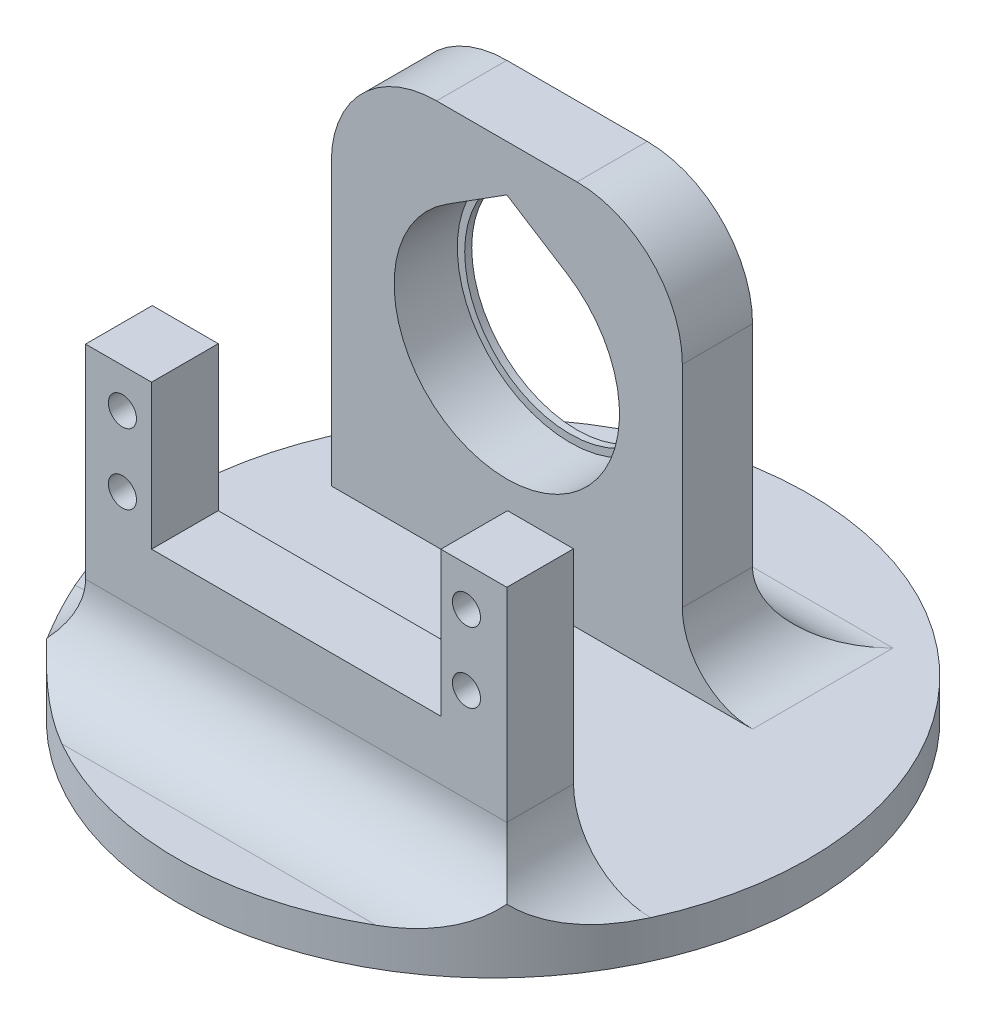
SolidWorks part; units mm, degrees
ref_plane "Front Plane" through (0, 0, 0) normal (0, 0, 1) x (1, 0, 0)
ref_plane "Top Plane" through (0, 0, 0) normal (0, 1, 0) x (1, 0, 0)
ref_plane "Right Plane" through (0, 0, 0) normal (1, 0, 0) x (0, 0, -1)
sketch "Sketch1" plane through (0, 0, 0) normal (0, 1, 0) x (1, 0, 0)
  circle A0 centre (0, 0) radius 45
  dimension "D1" = 90
extrude "Boss-Extrude1" add sketch "Sketch1" along normal blind 5.4
sketch "Sketch2" plane through (0, 0, 0) normal (0, -1, 0) x (1, 0, 0)
  circle A0 centre (0, 0) radius 10.5
  dimension "D1" = 21
extrude "Cut-Extrude1" cut sketch "Sketch2" against normal blind 3.4
sketch "Sketch4" plane through (0, 5.4, 0) normal (0, 1, 0) x (1, 0, 0)
  circle A0 centre (0, 0) radius 4.875
  dimension "D1" = 9.75
extrude "Cut-Extrude2" cut sketch "Sketch4" against normal blind 22.5
sketch "Sketch5" plane through (0, 5.4, 0) normal (0, 1, 0) x (1, 0, 0)
  line L1 (-30, -18.541) -> (30, -18.541)
  line L2 (-30, -18.541) -> (-30, -28.041)
  line L3 (-30, -28.041) -> (30, -28.041)
  line L4 (30, -18.541) -> (30, -28.041)
  point P4 (0, -18.541)
  dimension "D1" = 60
  dimension "D2" = 18.541
  dimension "D3" = 9.5
extrude "Boss-Extrude2" add sketch "Sketch5" along normal blind 40
sketch "Sketch6" plane through (0, 45.4, 0) normal (0, 1, 0) x (1, 0, 0)
  line L1 (-20.6, 8.6801) -> (20.6, 8.6801)
  line L2 (-20.6, 8.6801) -> (-20.6, -51.928)
  line L3 (-20.6, -51.928) -> (20.6, -51.928)
  line L4 (20.6, 8.6801) -> (20.6, -51.928)
  line L5 (-20.6, 8.6801) -> (20.6, -51.928) construction
  line L6 (-20.6, -51.928) -> (20.6, 8.6801) construction
  point P0 (0, -21.624)
  dimension "D1" = 41.2
extrude "Cut-Extrude3" cut sketch "Sketch6" against normal blind 20.6
fillet "Fillet2" radius 11 3 edges at (0, 5.4, 28.041) (-30, 5.4, 23.291) (30, 5.4, 23.291)
sketch "Sketch7" plane through (0, 5.4, 0) normal (0, 1, 0) x (1, 0, 0)
  line L0 (-10, 4.459) -> (0.8781, -33.8396) construction
  line L1 (-35, 21.959) -> (15, 21.959)
  line L2 (-35, 21.959) -> (-35, 11.959)
  line L3 (-35, 11.959) -> (15, 11.959)
  line L4 (15, 21.959) -> (15, 11.959)
  line L5 (-35, 21.959) -> (15, 11.959) construction
  line L6 (-35, 11.959) -> (15, 21.959) construction
  line L7 (-10, 4.459) -> (0.8781, -33.8396) construction
  point P0 (-10, 16.959)
  point P14 (-10, 4.459)
  dimension "D1" = 50
  dimension "D2" = 10
  dimension "D3" = 12.5
extrude "Boss-Extrude3" add sketch "Sketch7" along normal blind 55
sketch "Sketch8" plane through (0, 0, -21.959) normal (0, 0, -1) x (-1, 0, 0)
  line L0 (35, 60.4) -> (35, 5.4) construction
  line L2 (-15, 5.4) -> (35, 5.4) construction
  circle A0 centre (10.0003, 34.8) radius 15
  dimension "D1" = 24.9997
  dimension "D3" = 30
  dimension "D2" = 29.4
extrude "Cut-Extrude4" cut sketch "Sketch8" against normal blind 18.6
sketch "Sketch9" plane through (0, 0, -11.959) normal (0, 0, 1) x (1, 0, 0)
  line L0 (-10.0003, 34.8) -> (-10.0003, 53.8) construction
  line L1 (-10.0003, 53.8) -> (-18.5899, 48.358)
  line L2 (-10.0003, 53.8) -> (-1.4106, 48.358)
  arc A0 (-18.5899, 48.358) -> (-1.4106, 48.358) centre (-10.0003, 34.8) ccw
  point P6 (0, 0)
  point P7 (0, 0)
  dimension "D1" = 32.1
  dimension "D2" = 19
extrude "Cut-Extrude5" cut sketch "Sketch9" against normal offset from surface (9 mm away) 1 up to face at (-25.0003, 34.8, -21.959)
fillet "Fillet4" radius 15 2 edges at (-35, 60.4, -16.959) (15, 60.4, -16.959)
fillet "Fillet5" radius 10 2 edges at (-10, 5.4, -21.959) (15, 5.4, -16.959)
sketch "Sketch10" plane through (0, 5.4, 0) normal (0, 1, 0) x (1, 0, 0)
  circle A0 centre (7, 0) radius 1.65
  circle A1 centre (0, 7) radius 1.65
  circle A2 centre (-7, 0) radius 1.65
  circle A3 centre (0, -7) radius 1.65
  dimension "D1" = 7
  dimension "D2" = 7
  dimension "D5" = 3.3
  dimension "D3" = 7
  dimension "D4" = 7
extrude "Cut-Extrude6" cut sketch "Sketch10" against normal through all both and the other way through all
sketch "Sketch11" plane through (0, 0, 18.541) normal (0, 0, -1) x (-1, 0, 0)
  line L0 (-20.6, 24.8) -> (20.6, 24.8) construction
  line L2 (20.6, 45.4) -> (20.6, 24.8) construction
  circle A0 centre (24.7503, 39.8) radius 2
  circle A1 centre (24.7503, 29.8) radius 2
  circle A2 centre (-24.2497, 29.8) radius 2
  circle A3 centre (-24.2497, 39.8) radius 2
  dimension "D1" = 10
  dimension "D3" = 4
  dimension "D2" = 4.1503
  dimension "D4" = 15
  dimension "D5" = 49
extrude "Cut-Extrude7" cut sketch "Sketch11" against normal blind 34
